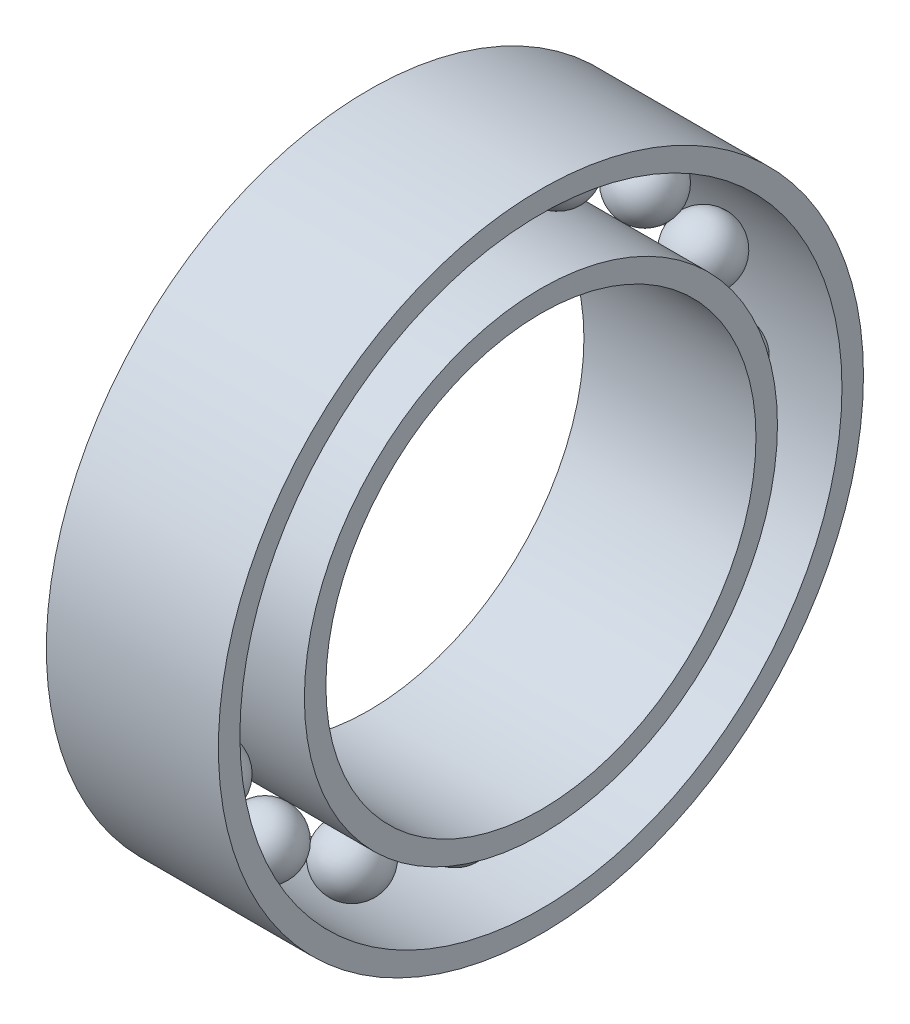
SolidWorks part; units mm, degrees
material "铸造合金钢"
ref_plane "前视基准面" through (0, 0, 0) normal (0, 0, 1) x (1, 0, 0)
ref_plane "上视基准面" through (0, 0, 0) normal (0, 1, 0) x (1, 0, 0)
ref_plane "右视基准面" through (0, 0, 0) normal (1, 0, 0) x (0, 0, -1)
sketch "草图1" plane through (0, 0, 0) normal (1, 0, 0) x (0, 0, -1)
  line L0 (0, 7) -> (0, 5.5)
  line L1 (2.6788, 6.4672) -> (2.1048, 5.0813)
  line L2 (4.9497, 4.9497) -> (3.8891, 3.8891)
  line L3 (6.4672, 2.6788) -> (5.0813, 2.1048)
  line L4 (7, 0) -> (5.5, 0)
  line L5 (6.4672, -2.6788) -> (5.0813, -2.1048)
  line L6 (4.9497, -4.9497) -> (3.8891, -3.8891)
  line L7 (2.6788, -6.4672) -> (2.1048, -5.0813)
  line L8 (0, -7) -> (0, -5.5)
  line L9 (-2.6788, -6.4672) -> (-2.1048, -5.0813)
  line L10 (-4.9497, -4.9497) -> (-3.8891, -3.8891)
  line L11 (-6.4672, -2.6788) -> (-5.0813, -2.1048)
  line L12 (-7, 0) -> (-5.5, 0)
  line L13 (-6.4672, 2.6788) -> (-5.0813, 2.1048)
  line L14 (-4.9497, 4.9497) -> (-3.8891, 3.8891)
  line L15 (-2.6788, 6.4672) -> (-2.1048, 5.0813)
  circle A0 centre (0, 0) radius 5
  circle A1 centre (0, 0) radius 5.5
  circle A2 centre (0, 0) radius 7
  circle A3 centre (0, 0) radius 7.5
  circle A4 centre (0, 6.25) radius 0.75
  circle A5 centre (2.3918, 5.7742) radius 0.75
  circle A6 centre (4.4194, 4.4194) radius 0.75
  circle A7 centre (5.7742, 2.3918) radius 0.75
  circle A8 centre (6.25, 0) radius 0.75
  circle A9 centre (5.7742, -2.3918) radius 0.75
  circle A10 centre (4.4194, -4.4194) radius 0.75
  circle A11 centre (2.3918, -5.7742) radius 0.75
  circle A12 centre (0, -6.25) radius 0.75
  circle A13 centre (-2.3918, -5.7742) radius 0.75
  circle A14 centre (-4.4194, -4.4194) radius 0.75
  circle A15 centre (-5.7742, -2.3918) radius 0.75
  circle A16 centre (-6.25, 0) radius 0.75
  circle A17 centre (-5.7742, 2.3918) radius 0.75
  circle A18 centre (-4.4194, 4.4194) radius 0.75
  circle A19 centre (-2.3918, 5.7742) radius 0.75
  circle A20 centre (0, 0) radius 6.25
  point P42 (0, 0)
  point P74 (0, 0)
  dimension "D1" = 10
  dimension "D2" = 11
  dimension "D3" = 14
  dimension "D4" = 15
  dimension "D5" = 16
  dimension "D6" = 16
revolve "旋转1" add sketch "草图1" angle 360 about L0 region at (0, 6.5601, -0.3244) region at (0, 5.9237, -0.3119)
extrude "凸台-拉伸1" add sketch "草图1<4>" along normal blind 2 and the other way blind 2 separate body contours A1 A0 | A3 A2 region at (0, 5.2417, -1.0426) region at (0, 0, 7.2879)
sketch "草图1<4>" plane through (0, 0, 0) normal (1, 0, 0) x (0, 0, -1) same geometry as "草图1"
pattern_circular "阵列(圆周)6" count 16 over 360 about axis through (2, 0, 0) along (1, 0, 0) of bodies 106
